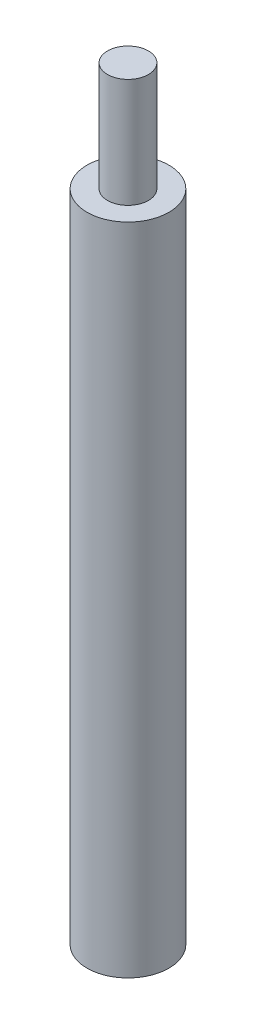
SolidWorks part; units mm, degrees
ref_plane "Front Plane" through (0, 0, 0) normal (0, 0, 1) x (1, 0, 0)
ref_plane "Top Plane" through (0, 0, 0) normal (0, 1, 0) x (1, 0, 0)
ref_plane "Right Plane" through (0, 0, 0) normal (1, 0, 0) x (0, 0, -1)
sketch "Sketch1" plane through (0, 0, 0) normal (0, 1, 0) x (1, 0, 0)
  circle A0 centre (0, 0) radius 2.3813
  dimension "D1" = 4.7625
extrude "Boss-Extrude1" add sketch "Sketch1" against normal blind 12.7
sketch "Sketch2" plane through (0, -12.7, 0) normal (0, -1, 0) x (-1, 0, 0)
  circle A0 centre (0, 0) radius 4.7625
  dimension "D1" = 9.525
extrude "Boss-Extrude2" add sketch "Sketch2" along normal blind 76.2
